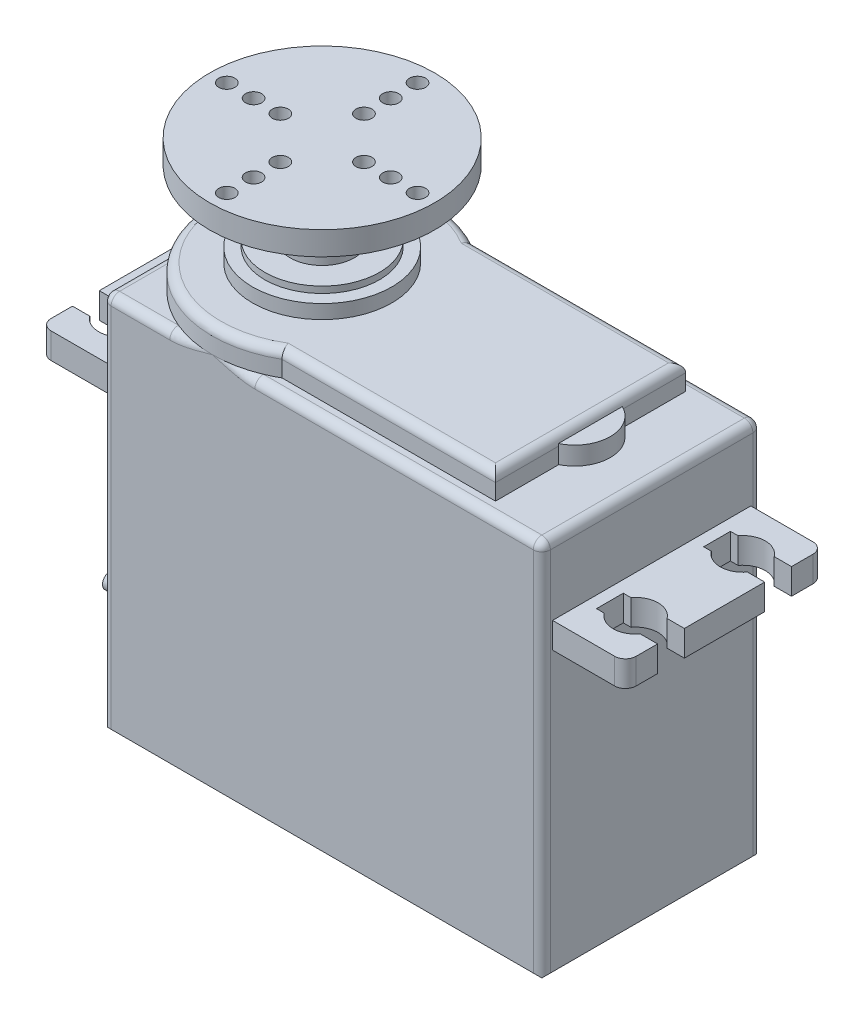
SolidWorks part; units mm, degrees
ref_plane "前视基准面" through (0, 0, 0) normal (0, 0, 1) x (1, 0, 0)
ref_plane "上视基准面" through (0, 0, 0) normal (0, 1, 0) x (1, 0, 0)
ref_plane "右视基准面" through (0, 0, 0) normal (1, 0, 0) x (0, 0, -1)
sketch "草图2" plane through (0, 0, 0) normal (0, 1, 0) x (1, 0, 0)
  line L1 (-20.5, 10.25) -> (20.5, 10.25)
  line L2 (-20.5, 10.25) -> (-20.5, -10.25)
  line L3 (-20.5, -10.25) -> (20.5, -10.25)
  line L4 (20.5, 10.25) -> (20.5, -10.25)
  line L5 (0, -10.25) -> (0, 10.25) construction
  line L6 (-20.5, 0) -> (20.5, 0) construction
  point P0 (0, 0)
  dimension "D1" = 41
  dimension "D2" = 20.5
extrude "凸台-拉伸1" add sketch "草图2" along normal blind 37
chamfer "倒角1" distance 2 angle 45 4 edges at (-20.5, 0, 0) (0, 0, -10.25) (20.5, 0, 0) (0, 0, 10.25)
sketch "草图3" plane through (0, 37, 0) normal (0, 1, 0) x (1, 0, 0)
  line L0 (-5.122, 8.875) -> (14.8, 8.875)
  line L1 (14.8, 8.875) -> (14.8, 2.9719)
  line L2 (14.8, -8.875) -> (-5.122, -8.875)
  line L3 (0, 0) -> (24.9336, 0) construction
  line L4 (20.5, 10.25) -> (-20.5, 10.25) construction
  line L5 (-20.5, 10.25) -> (-20.5, -10.25) construction
  line L6 (-20.5, -10.25) -> (20.5, -10.25) construction
  line L7 (20.5, -10.25) -> (20.5, 10.25) construction
  line L8 (14.8, -2.9719) -> (14.8, -8.875)
  arc A0 (-5.122, 8.875) -> (-5.122, -8.875) centre (-10.25, 0) ccw
  arc A1 (14.8, -2.9719) -> (14.8, 2.9719) centre (13.32, 0) ccw
  dimension "D2" = 6.64
  dimension "D3" = 1.48
  dimension "D1" = 17.75
  dimension "D4" = 5.7
extrude "凸台-拉伸2" add sketch "草图3" along normal blind 2.3
sketch "草图4" plane through (0, 39.3, 0) normal (0, 1, 0) x (1, 0, 0)
  line L0 (14.8, 2.9719) -> (14.8, -2.9719)
  arc A0 (14.8, -2.9719) -> (14.8, 2.9719) centre (13.32, 0) ccw construction
  arc A1 (14.8, -2.9719) -> (14.8, 2.9719) centre (13.32, 0) ccw
extrude "切除-拉伸1" cut sketch "草图4" against normal blind 0.6
sketch "草图5" plane through (0, 39.3, 0) normal (0, 1, 0) x (1, 0, 0)
  circle A0 centre (-10.25, 0) radius 6.5
  dimension "D1" = 13
extrude "凸台-拉伸3" add sketch "草图5" along normal blind 1.3
sketch "草图6" plane through (0, 40.6, 0) normal (0, 1, 0) x (1, 0, 0)
  circle A0 centre (-10.25, 0) radius 5.35
  dimension "D1" = 10.7
extrude "凸台-拉伸4" add sketch "草图6" along normal blind 0.6
sketch "草图7" plane through (0, 41.2, 0) normal (0, 1, 0) x (1, 0, 0)
  circle A0 centre (-10.25, 0) radius 3
  dimension "D1" = 6
extrude "凸台-拉伸5" add sketch "草图7" along normal blind 6
sketch "草图8" plane through (0, 47.2, 0) normal (0, 1, 0) x (1, 0, 0)
  circle A0 centre (-10.25, 0) radius 10.5
  point P5 (-10.25, 0)
  dimension "D1" = 21
extrude "凸台-拉伸6" add sketch "草图8" along normal blind 2.2
sketch "草图9" plane through (0, 49.4, 0) normal (0, 1, 0) x (1, 0, 0)
  line L1 (-10.25, 0) -> (-20.75, 0) construction
  circle A2 centre (-14.15, 0) radius 0.75
  circle A3 centre (-10.25, 0) radius 10.5 construction
  circle A4 centre (-16.65, 0) radius 0.75
  circle A5 centre (-19.15, 0) radius 0.75
  dimension "D1" = 1.5
  dimension "D2" = 2.5
  dimension "D5" = 1.5
  dimension "D6" = 1.5
  dimension "D3" = 2.5
  dimension "D4" = 3.9
extrude "切除-拉伸2" cut sketch "草图9" against normal up to next
pattern_circular "阵列(圆周)1" count 4 over 360 about axis through (-10.25, 49.4, 0) along (0, 1, 0) of "切除-拉伸2"
sketch "草图10" plane through (-20.5, 0, 0) normal (-1, 0, 0) x (0, 0, 1)
  line L1 (-3.5, 7.4) -> (3.5, 7.4)
  line L2 (-3.5, 7.4) -> (-3.5, 3.2)
  line L3 (-3.5, 3.2) -> (3.5, 3.2)
  line L4 (3.5, 7.4) -> (3.5, 3.2)
  line L5 (0, 3.2) -> (0, 7.4) construction
  line L6 (-3.5, 5.3) -> (3.5, 5.3) construction
  line L7 (8.25, 0) -> (-8.25, 0) construction
  line L8 (-10.25, 2) -> (10.25, 2) construction
  point P0 (0, 5.3)
  point P8 (0, 2)
  dimension "D1" = 4.2
  dimension "D2" = 7
  dimension "D3" = 3.2
extrude "凸台-拉伸7" add sketch "草图10" along normal blind 1
sketch "草图12" plane through (-21.5, 0, 0) normal (-1, 0, 0) x (0, 0, 1)
  line L8 (3.15, 3.55) -> (3.15, 7.05)
  line L9 (3.15, 7.05) -> (-3.15, 7.05)
  line L10 (-3.15, 7.05) -> (-3.15, 3.55)
  line L11 (-3.15, 3.55) -> (3.15, 3.55)
  line L12 (3.15, 3.55) -> (3.15, 7.05)
  line L13 (3.15, 7.05) -> (-3.15, 7.05)
  line L14 (-3.15, 7.05) -> (-3.15, 3.55)
  line L15 (-3.15, 3.55) -> (3.15, 3.55)
  dimension "D1" = 0.35
extrude "凸台-拉伸8" add sketch "草图12" along normal blind 4 draft 5
sketch "草图13" plane through (-25.5, 0, 0) normal (-1, 0, 0) x (0, 0, 1)
  line L0 (-2.8, 3.9) -> (2.8, 3.9) construction
  circle A0 centre (0, 5.3) radius 0.75
  circle A1 centre (1.5, 5.3) radius 0.75
  circle A2 centre (-1.5, 5.3) radius 0.75
  point P9 (0, 3.9)
  dimension "D1" = 1.5
  dimension "D2" = 1.4
  dimension "D3" = 1.4
  dimension "D4" = 1.4
extrude "凸台-拉伸9" add sketch "草图13" along normal blind 3 separate body contours A2 | A0 | A1
fillet "圆角1" radius 0.8 4 edges at (20.5, 19.5, -10.25) (-20.5, 19.5, -10.25) (20.5, 19.5, 10.25) (-20.5, 19.5, 10.25)
fillet "圆角2" radius 0.8 15 edges at (-20.2657, 37, -10.0157) (-14.975, 37, -10.25) (4.725, 37, -10.25) (20.2657, 37, -10.0157) (20.5, 37, 0) (20.2657, 37, 10.0157) (4.725, 37, 10.25) (-14.975, 37, 10.25) (-20.2657, 37, 10.0157) (-20.5, 37, 4.725) (-20.5, 37, -4.725) (14.8, 39.3, 0) (4.839, 39.3, -8.875) (4.839, 39.3, 8.875) (-20.5, 39.3, 0)
sketch "草图15" plane through (-20.5, 0, 0) normal (-1, 0, 0) x (0, 0, 1)
  line L0 (9.45, 36.2) -> (3.9699, 36.2) construction
  line L1 (-9.25, 30.4) -> (9.25, 30.4)
  line L2 (-9.25, 30.4) -> (-9.25, 28)
  line L3 (-9.25, 28) -> (9.25, 28)
  line L4 (9.25, 30.4) -> (9.25, 28)
  line L5 (0, 28) -> (0, 30.4) construction
  line L6 (-9.25, 29.2) -> (9.25, 29.2) construction
  line L7 (-10.25, 2) -> (-10.25, 36.2) construction
  point P0 (0, 29.2)
  dimension "D1" = 18.5
  dimension "D2" = 2.4
  dimension "D3" = 5.8
  dimension "D4" = 1
extrude "凸台-拉伸10" add sketch "草图15" along normal blind 6.8
fillet "圆角3" radius 1 2 edges at (-27.3, 29.2, -9.25) (-27.3, 29.2, 9.25)
sketch "草图16" plane through (0, 30.4, 0) normal (0, 1, 0) x (1, 0, 0)
  line L0 (-27.3, 0) -> (-19.7, 0) construction
  line L1 (-27.3, -8.25) -> (-27.3, 8.25) construction
  line L2 (-22.3125, 3.75) -> (-21.6, 3.75)
  line L3 (-27.3, 6.25) -> (-25.6875, 6.25)
  line L4 (-27.3, 6.25) -> (-27.3, 3.75)
  line L5 (-27.3, 3.75) -> (-25.6875, 3.75)
  line L6 (-21.6, 6.25) -> (-21.6, 3.75)
  line L7 (-22.3125, 6.25) -> (-21.6, 6.25)
  line L8 (-27.3, 5) -> (-21.6, 5) construction
  line L9 (-27.3, -6.25) -> (-25.6875, -6.25)
  line L10 (-27.3, -6.25) -> (-27.3, -3.75)
  line L11 (-27.3, -3.75) -> (-25.6875, -3.75)
  line L12 (-22.3125, -3.75) -> (-21.6, -3.75)
  line L13 (-21.6, -6.25) -> (-21.6, -3.75)
  line L14 (-22.3125, -6.25) -> (-21.6, -6.25)
  arc A0 (-5.3411, 8.075) -> (-5.3411, -8.075) centre (-10.25, 0) ccw construction
  arc A1 (-25.6875, 3.75) -> (-22.3125, 3.75) centre (-24, 5) ccw
  arc A2 (-22.3125, 6.25) -> (-25.6875, 6.25) centre (-24, 5) ccw
  arc A3 (-25.6875, -3.75) -> (-22.3125, -3.75) centre (-24, -5) cw
  arc A4 (-22.3125, -6.25) -> (-25.6875, -6.25) centre (-24, -5) cw
  point P7 (-24.45, 5)
  dimension "D2" = 4.2
  dimension "D3" = 3.3
  dimension "D1" = 2.5
  dimension "D4" = 5.7
  dimension "D5" = 5
  dimension "D6" = 0
extrude "切除-拉伸3" cut sketch "草图16" against normal up to next (2.4 mm away)
ref_plane "基准面4" through (0, 0, 0) normal (-1, 0, 0) x (0, 0, 1)
mirror "镜向1" about plane through (0, 0, 0) normal (-1, 0, 0) of "切除-拉伸3", "圆角3", "凸台-拉伸10"
